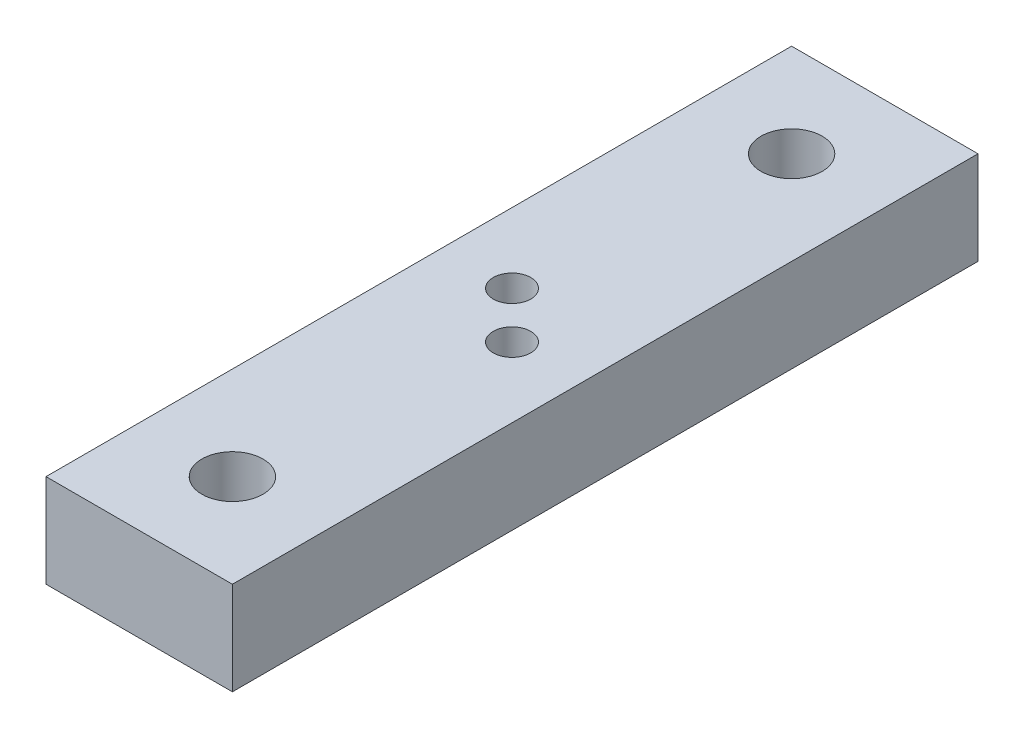
SolidWorks part; units mm, degrees
material "6061-T6 (SS)"
ref_plane "Front Plane" through (0, 0, 0) normal (0, 0, 1) x (1, 0, 0)
ref_plane "Top Plane" through (0, 0, 0) normal (0, 1, 0) x (1, 0, 0)
ref_plane "Right Plane" through (0, 0, 0) normal (1, 0, 0) x (0, 0, -1)
sketch "Sketch1" plane through (0, 0, 0) normal (0, 1, 0) x (1, 0, 0)
  line L1 (0, 0) -> (25.4, 0)
  line L2 (0, 0) -> (0, 101.6)
  line L3 (0, 101.6) -> (25.4, 101.6)
  line L4 (25.4, 0) -> (25.4, 101.6)
  circle A0 centre (12.7, 88.9) radius 4.1656
  circle A1 centre (12.7, 12.7) radius 4.1656
  dimension "D3" = 8.3312
  dimension "D4" = 8.3312
  dimension "D1" = 25.4
  dimension "D2" = 101.6
  dimension "D5" = 12.7
  dimension "D6" = 12.7
  dimension "D7" = 12.7
  dimension "D8" = 12.7
extrude "Boss-Extrude1" add sketch "Sketch1" along normal blind 12.7
hole_wizard "CBORE for #10 Hex Machine Screw1" positions "Sketch2" profile "Sketch3" counterbore size "#10" standard "ANSI Inch" end condition through all
sketch "Sketch2" plane through (0, 0, 0) normal (0, -1, 0) x (-1, 0, 0)
  line L0 (0, 101.6) -> (0, 0) construction
  point P0 (-15.875, 47.625)
  point P2 (-9.525, 53.975)
  dimension "D1" = 9.525
  dimension "D2" = 47.625
  dimension "D3" = 9.525
  dimension "D4" = 47.625
sketch "Sketch3" plane through (15.875, 0, -47.625) normal (1, 0, 0) x (0, 0, -1)
  line L0 (0, 0) -> (0, 12.7)
  line L1 (0, 12.7) -> (2.5527, 12.7)
  line L3 (2.5527, 12.7) -> (2.5527, 3.048)
  line L4 (2.5527, 3.048) -> (7.1437, 3.048)
  line L5 (7.1437, 3.048) -> (7.1438, 0)
  line L7 (7.1438, 0) -> (0, 0)
  line L11 (0, -6.35) -> (0, 107.95) construction
  dimension "Thru Hole Dia." = 5.1054
  dimension "Thru Hole Depth" = 12.7
  dimension "C'Bore Dia." = 14.2875
  dimension "C'Bore Depth" = 3.048
